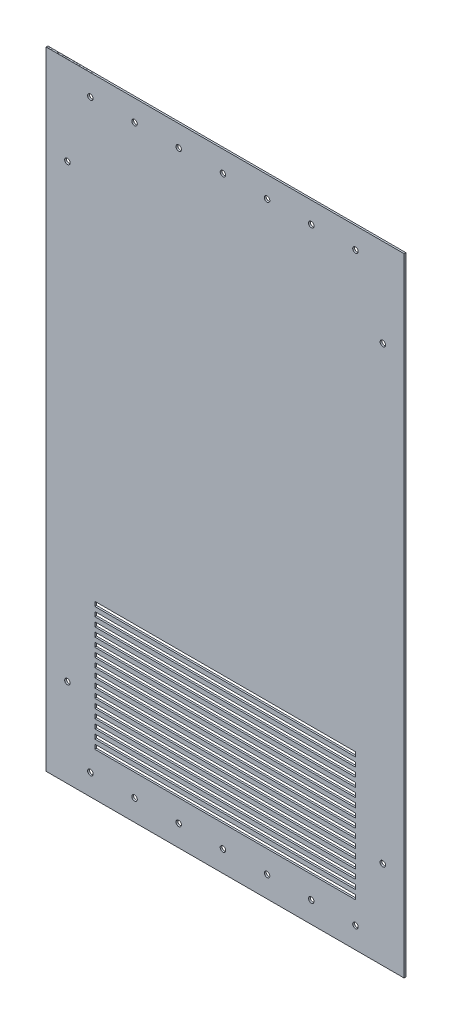
SolidWorks part; units mm, degrees
ref_plane "Front Plane" through (0, 0, 0) normal (0, 0, 1) x (1, 0, 0)
ref_plane "Top Plane" through (0, 0, 0) normal (0, 1, 0) x (1, 0, 0)
ref_plane "Right Plane" through (0, 0, 0) normal (1, 0, 0) x (0, 0, -1)
sketch "Sketch1" plane through (0, 0, 0) normal (0, 0, 1) x (1, 0, 0)
  line L0 (24, -100) -> (24, -571.3583) construction
  line L1 (0, 0) -> (405, 0)
  line L2 (0, 0) -> (0, -710)
  line L3 (0, -710) -> (405, -710)
  line L4 (405, 0) -> (405, -710)
  line L5 (24, -610) -> (381, -610) construction
  line L6 (381, -610) -> (381, -100) construction
  circle A0 centre (24, -100) radius 3.1
  circle A1 centre (381, -100) radius 3.1
  circle A2 centre (381, -610) radius 3.1
  circle A3 centre (24, -610) radius 3.1
  dimension "D8" = 6.2
  dimension "D1" = 405
  dimension "D2" = 710
  dimension "D3" = 24
  dimension "D4" = 100
  dimension "D5" = 24
  dimension "D6" = 100
  dimension "D7" = 100
extrude "Boss-Extrude1" add sketch "Sketch1" along normal blind 2
sketch "Sketch2" plane through (0, 0, 2) normal (0, 0, 1) x (1, 0, 0)
  line L0 (50, -24) -> (355, -24) construction
  line L1 (405, 0) -> (0, 0) construction
  line L2 (0, 0) -> (0, -710) construction
  line L3 (405, -710) -> (405, 0) construction
  line L4 (0, -355) -> (405, -355) construction
  line L5 (50, -686) -> (355, -686) construction
  circle A0 centre (50, -24) radius 3.1
  circle A1 centre (100, -24) radius 3.1
  circle A2 centre (150, -24) radius 3.1
  circle A3 centre (200, -24) radius 3.1
  circle A4 centre (250, -24) radius 3.1
  circle A5 centre (300, -24) radius 3.1
  circle A6 centre (350, -24) radius 3.1
  circle A7 centre (300, -686) radius 3.1
  circle A8 centre (250, -686) radius 3.1
  circle A9 centre (200, -686) radius 3.1
  circle A10 centre (150, -686) radius 3.1
  circle A11 centre (100, -686) radius 3.1
  circle A12 centre (50, -686) radius 3.1
  circle A13 centre (350, -686) radius 3.1
  dimension "D4" = 6.2
  dimension "D1" = 24
  dimension "D2" = 50
  dimension "D3" = 50
  dimension "D5" = 7
extrude "Cut-Extrude1" cut sketch "Sketch2" against normal through all
sketch "Sketch3" plane through (0, 0, 2) normal (0, 0, 1) x (1, 0, 0)
  line L0 (345.4109, -755.089) -> (399.6973, -755.089) construction
  line L1 (349.0904, -752.2312) -> (348.8156, -752.4415)
  line L2 (348.8156, -754.2364) -> (349.0904, -754.4446)
  line L3 (352.9045, -752.5313) -> (353.2186, -752.5313)
  line L4 (353.2186, -752.5313) -> (353.2186, -752.9758)
  line L5 (356.7186, -753.7035) -> (356.7186, -755.089)
  line L6 (356.7186, -755.089) -> (356.4045, -755.089)
  line L7 (356.4045, -755.089) -> (356.4045, -753.7021)
  line L8 (354.9686, -754.0941) -> (354.9686, -755.089)
  line L9 (354.9686, -755.089) -> (354.6545, -755.089)
  line L10 (354.6545, -755.089) -> (354.6545, -753.7884)
  line L11 (353.2186, -754.0127) -> (353.2186, -755.089)
  line L12 (353.2186, -755.089) -> (352.9045, -755.089)
  line L13 (352.9045, -755.089) -> (352.9045, -752.5313)
  line L14 (357.4366, -752.5313) -> (357.7507, -752.5313)
  line L15 (357.7507, -752.5313) -> (357.7507, -753.0045)
  line L16 (357.7507, -754.6255) -> (357.7507, -756.0313)
  line L17 (357.7507, -756.0313) -> (357.4366, -756.0313)
  line L18 (357.4366, -756.0313) -> (357.4366, -752.5313)
  line L19 (360.6673, -752.5313) -> (360.9814, -752.5313)
  line L20 (360.9814, -752.5313) -> (360.9814, -752.9078)
  line L21 (361.8789, -752.574) -> (361.7064, -752.8461)
  line L22 (360.9814, -754.2294) -> (360.9814, -755.089)
  line L23 (360.9814, -755.089) -> (360.6673, -755.089)
  line L24 (360.6673, -755.089) -> (360.6673, -752.5313)
  line L25 (364.2921, -754.2813) -> (364.5712, -754.4278)
  line L26 (364.7058, -753.8774) -> (362.4173, -753.8774)
  line L27 (362.4503, -753.5633) -> (364.3917, -753.5633)
  line L28 (366.5455, -752.8503) -> (366.3324, -753.0697)
  line L29 (365.1096, -754.7875) -> (365.3179, -754.5505)
  line L30 (368.4302, -752.8503) -> (368.217, -753.0697)
  line L31 (366.9943, -754.7875) -> (367.2025, -754.5505)
  line L32 (372.1994, -752.5313) -> (372.5135, -752.5313)
  line L33 (372.5135, -752.5313) -> (372.5135, -752.9078)
  line L34 (373.4109, -752.574) -> (373.2384, -752.8461)
  line L35 (372.5135, -754.2294) -> (372.5135, -755.089)
  line L36 (372.5135, -755.089) -> (372.1994, -755.089)
  line L37 (372.1994, -755.089) -> (372.1994, -752.5313)
  line L38 (376.2827, -752.8503) -> (376.0696, -753.0697)
  line L39 (374.8468, -754.7875) -> (375.0551, -754.5505)
  line L40 (376.9109, -752.5313) -> (377.225, -752.5313)
  line L41 (377.225, -752.5313) -> (377.225, -755.089)
  line L42 (377.225, -755.089) -> (376.9109, -755.089)
  line L43 (376.9109, -755.089) -> (376.9109, -752.5313)
  line L44 (380.5904, -751.4992) -> (380.5904, -755.089)
  line L45 (380.5904, -755.089) -> (380.2763, -755.089)
  line L46 (380.2763, -755.089) -> (380.2763, -754.6465)
  line L47 (380.2763, -753.0263) -> (380.2763, -751.4992)
  line L48 (380.2763, -751.4992) -> (380.5904, -751.4992)
  line L49 (383.4075, -754.2813) -> (383.6866, -754.4278)
  line L50 (383.8212, -753.8774) -> (381.5327, -753.8774)
  line L51 (381.5657, -753.5633) -> (383.5071, -753.5633)
  line L52 (388.3084, -753.0858) -> (388.0454, -753.2492)
  line L53 (388.0454, -754.371) -> (388.3084, -754.5435)
  line L54 (391.8532, -752.5313) -> (392.1933, -752.5313)
  line L55 (392.1933, -752.5313) -> (393.0423, -754.3934)
  line L56 (393.0423, -754.3934) -> (393.8914, -752.5313)
  line L57 (393.8914, -752.5313) -> (394.2314, -752.5313)
  line L58 (394.2314, -752.5313) -> (393.0648, -755.089)
  line L59 (393.0648, -755.089) -> (393.0199, -755.089)
  line L60 (393.0199, -755.089) -> (391.8532, -752.5313)
  line L61 (396.8691, -754.2813) -> (397.1481, -754.4278)
  line L62 (397.2827, -753.8774) -> (394.9943, -753.8774)
  line L63 (395.0272, -753.5633) -> (396.9686, -753.5633)
  line L64 (397.8212, -752.5313) -> (398.1353, -752.5313)
  line L65 (398.1353, -752.5313) -> (398.1353, -752.9078)
  line L66 (399.0327, -752.574) -> (398.8602, -752.8461)
  line L67 (398.1353, -754.2294) -> (398.1353, -755.089)
  line L68 (398.1353, -755.089) -> (397.8212, -755.089)
  line L69 (397.8212, -755.089) -> (397.8212, -752.5313)
  spline S0 degree 3 poles (348.8156, -752.4415) (348.7773, -752.3945) (348.7167, -752.3273) (348.629, -752.2455) (348.5611, -752.1882) (348.4894, -752.1368) (348.4155, -752.0886) (348.3383, -752.0453) (348.2316, -751.9928) (348.0919, -751.9381) (347.8544, -751.8758) (347.6689, -751.8576) (347.5437, -751.8582) knots 0 0 0 0 0.125475 0.187121 0.248294 0.309295 0.36985 0.430973 0.492456 0.616148 0.740844 1 1 1 1
  spline S1 degree 3 poles (347.5437, -751.8582) (347.4739, -751.8573) (347.3699, -751.8648) (347.2334, -751.8849) (347.1337, -751.907) (347.0362, -751.935) (346.9401, -751.9684) (346.8469, -752.0098) (346.7552, -752.0555) (346.6675, -752.1071) (346.5844, -752.1634) (346.5064, -752.2238) (346.4333, -752.2885) (346.3651, -752.3571) (346.3023, -752.4305) (346.2452, -752.5083) (346.1924, -752.5896) (346.1452, -752.6742) (346.1057, -752.7622) (346.0707, -752.8524) (346.043, -752.9455) (346.0211, -753.041) (346.0006, -753.1732) (345.9934, -753.2742) (345.9943, -753.3425) knots 0 0 0 0 0.087502 0.130463 0.172752 0.215403 0.25765 0.300153 0.343121 0.385925 0.427686 0.468818 0.509492 0.549883 0.58998 0.630405 0.670869 0.711384 0.751627 0.791776 0.832459 0.873319 0.914543 1 1 1 1
  spline S2 degree 3 poles (345.9943, -753.3425) (345.9938, -753.4441) (346.0079, -753.5941) (346.0536, -753.787) (346.1038, -753.9224) (346.1657, -754.0523) (346.2439, -754.1746) (346.3345, -754.291) (346.4388, -754.3988) (346.5532, -754.4974) (346.676, -754.5841) (346.8068, -754.6564) (346.9441, -754.7166) (347.0892, -754.7628) (347.2958, -754.8072) (347.4565, -754.8206) (347.5655, -754.8197) knots 0 0 0 0 0.12629 0.186726 0.246146 0.305576 0.365429 0.426326 0.48884 0.551725 0.613919 0.675484 0.737334 0.800229 0.864502 1 1 1 1
  spline S3 degree 3 poles (347.5655, -754.8197) (347.6856, -754.8198) (347.8641, -754.8028) (348.092, -754.7408) (348.2534, -754.677) (348.4067, -754.5939) (348.6042, -754.4576) (348.7349, -754.3292) (348.8156, -754.2364) knots 0 0 0 0 0.252949 0.374755 0.49594 0.617181 0.740909 1 1 1 1
  spline S4 degree 3 poles (349.0904, -754.4446) (349.0471, -754.5022) (348.9783, -754.5848) (348.8774, -754.6859) (348.7978, -754.756) (348.7147, -754.8222) (348.6266, -754.8825) (348.5347, -754.9378) (348.4394, -754.9884) (348.3406, -755.0333) (348.2386, -755.0718) (348.1338, -755.1049) (348.0261, -755.1321) (347.9154, -755.1534) (347.7626, -755.1727) (347.646, -755.1793) (347.5676, -755.1787) knots 0 0 0 0 0.123053 0.183475 0.243727 0.304279 0.364863 0.425946 0.487391 0.54922 0.611144 0.673529 0.736961 0.800785 0.866013 1 1 1 1
  spline S5 degree 3 poles (347.5676, -755.1787) (347.4931, -755.1796) (347.383, -755.1737) (347.2386, -755.1581) (347.1348, -755.1408) (347.0337, -755.1205) (346.9361, -755.0932) (346.8412, -755.0627) (346.7492, -755.0268) (346.6602, -754.9863) (346.5743, -754.9405) (346.4917, -754.8898) (346.4115, -754.8353) (346.3349, -754.7753) (346.236, -754.6887) (346.167, -754.6173) (346.124, -754.5666) knots 0 0 0 0 0.13775 0.203917 0.26878 0.332414 0.394754 0.45618 0.516996 0.577396 0.637198 0.696999 0.756756 0.816554 0.876948 1 1 1 1
  spline S6 degree 3 poles (346.124, -754.5666) (346.0514, -754.4819) (345.954, -754.3461) (345.8508, -754.1497) (345.7884, -753.9964) (345.7397, -753.8363) (345.6937, -753.6109) (345.6798, -753.4365) (345.6802, -753.3186) knots 0 0 0 0 0.247156 0.36878 0.490734 0.613614 0.738958 1 1 1 1
  spline S7 degree 3 poles (345.6802, -753.3186) (345.6801, -753.1948) (345.6958, -753.0113) (345.7526, -752.7759) (345.812, -752.6097) (345.8873, -752.4505) (345.9803, -752.2997) (346.09, -752.1562) (346.2154, -752.0222) (346.353, -751.8996) (346.5003, -751.7918) (346.6571, -751.7021) (346.8216, -751.6271) (346.9951, -751.5695) (347.2417, -751.5146) (347.4336, -751.4995) (347.5634, -751.4992) knots 0 0 0 0 0.127014 0.187955 0.248014 0.307748 0.368235 0.42947 0.492743 0.556258 0.618217 0.679655 0.741246 0.803415 0.866815 1 1 1 1
  spline S8 degree 3 poles (347.5634, -751.4992) (347.6429, -751.4991) (347.7611, -751.5045) (347.9156, -751.5255) (348.0272, -751.5466) (348.1363, -751.5728) (348.2421, -751.6069) (348.3452, -751.646) (348.445, -751.6909) (348.5409, -751.7414) (348.6329, -751.7968) (348.7204, -751.8571) (348.8039, -751.9218) (348.882, -751.9922) (348.9822, -752.0913) (349.0482, -752.1745) (349.0904, -752.2312) knots 0 0 0 0 0.135683 0.201215 0.265682 0.329267 0.392395 0.45507 0.517127 0.57879 0.63974 0.700192 0.759806 0.819628 0.879355 1 1 1 1
  spline S9 degree 3 poles (350.954, -752.4864) (351.0481, -752.4854) (351.1873, -752.499) (351.3654, -752.5436) (351.4912, -752.5888) (351.6096, -752.6496) (351.762, -752.7471) (351.8636, -752.8398) (351.9257, -752.9078) knots 0 0 0 0 0.258332 0.382134 0.503804 0.624693 0.746871 1 1 1 1
  spline S10 degree 3 poles (351.9257, -752.9078) (351.9828, -752.9701) (352.0592, -753.07) (352.1414, -753.2144) (352.1905, -753.3266) (352.2292, -753.443) (352.2663, -753.6059) (352.2758, -753.7322) (352.2763, -753.8171) knots 0 0 0 0 0.253834 0.376506 0.498534 0.621368 0.744565 1 1 1 1
  spline S11 degree 3 poles (352.2763, -753.8171) (352.2768, -753.9027) (352.2651, -754.0298) (352.2265, -754.1942) (352.1857, -754.3121) (352.1333, -754.4259) (352.0694, -754.5353) (351.9936, -754.6405) (351.9076, -754.7405) (351.8125, -754.8327) (351.7094, -754.913) (351.6002, -754.9818) (351.4836, -755.0373) (351.3605, -755.0809) (351.1845, -755.1228) (351.0469, -755.1335) (350.954, -755.1338) knots 0 0 0 0 0.123337 0.183265 0.243172 0.302898 0.363774 0.425605 0.489659 0.553785 0.616222 0.677854 0.739517 0.802097 0.865866 1 1 1 1
  spline S12 degree 3 poles (350.954, -755.1338) (350.8606, -755.1334) (350.7226, -755.1229) (350.546, -755.0809) (350.4228, -755.0371) (350.3057, -754.9818) (350.1959, -754.9132) (350.0927, -754.8326) (349.9976, -754.7405) (349.9116, -754.6405) (349.8357, -754.5353) (349.7719, -754.4259) (349.7195, -754.3121) (349.6787, -754.1942) (349.6401, -754.0298) (349.6284, -753.9027) (349.6289, -753.8171) knots 0 0 0 0 0.134635 0.198324 0.260825 0.322714 0.384555 0.446913 0.510958 0.574931 0.636685 0.697483 0.757134 0.816966 0.876818 1 1 1 1
  spline S13 degree 3 poles (349.6289, -753.8171) (349.6294, -753.7324) (349.6389, -753.6064) (349.6759, -753.4439) (349.7146, -753.328) (349.7642, -753.2162) (349.8453, -753.0715) (349.923, -752.9724) (349.9794, -752.9099) knots 0 0 0 0 0.255238 0.378679 0.501088 0.622714 0.746241 1 1 1 1
  spline S14 degree 3 poles (349.9794, -752.9099) (350.041, -752.841) (350.1436, -752.7492) (350.2956, -752.6497) (350.4153, -752.5901) (350.5409, -752.5434) (350.7198, -752.499) (350.8594, -752.4855) (350.954, -752.4864) knots 0 0 0 0 0.252713 0.374819 0.496436 0.617911 0.741288 1 1 1 1
  spline S15 degree 3 poles (350.9526, -752.8005) (350.8856, -752.8007) (350.7861, -752.8097) (350.6581, -752.8408) (350.5667, -752.8734) (350.479, -752.9155) (350.3951, -752.9672) (350.3147, -753.0278) (350.2393, -753.0973) (350.1701, -753.1732) (350.1096, -753.254) (350.0582, -753.3385) (350.0154, -753.4268) (349.9835, -753.5197) (349.952, -753.6499) (349.9432, -753.7511) (349.943, -753.8192) knots 0 0 0 0 0.126044 0.187165 0.247399 0.30838 0.36978 0.432584 0.497641 0.562401 0.625557 0.687332 0.748313 0.809791 0.871768 1 1 1 1
  spline S16 degree 3 poles (349.943, -753.8192) (349.9432, -753.9079) (349.9588, -754.0412) (350.0171, -754.2092) (350.0757, -754.3288) (350.1491, -754.4395) (350.2356, -754.5382) (350.3342, -754.6233) (350.4438, -754.694) (350.5622, -754.7501) (350.7306, -754.804) (350.8633, -754.8207) (350.9526, -754.8197) knots 0 0 0 0 0.168179 0.251488 0.335841 0.419834 0.502345 0.583649 0.665931 0.748717 0.831047 1 1 1 1
  spline S17 degree 3 poles (350.9526, -754.8197) (351.0419, -754.8206) (351.1744, -754.8042) (351.3425, -754.7499) (351.4607, -754.6941) (351.5703, -754.6231) (351.6696, -754.5386) (351.7554, -754.4392) (351.8287, -754.3287) (351.8882, -754.2094) (351.9462, -754.0412) (351.962, -753.9079) (351.9622, -753.8192) knots 0 0 0 0 0.168983 0.250908 0.333708 0.416005 0.49766 0.579893 0.663902 0.748466 0.831791 1 1 1 1
  spline S18 degree 3 poles (351.9622, -753.8192) (351.962, -753.7511) (351.9531, -753.6499) (351.9217, -753.5197) (351.8898, -753.4268) (351.8471, -753.3383) (351.7947, -753.2543) (351.7345, -753.1729) (351.6644, -753.0975) (351.5891, -753.0278) (351.5087, -752.9672) (351.4249, -752.9157) (351.3375, -752.873) (351.2461, -752.8411) (351.1185, -752.8095) (351.0193, -752.8008) (350.9526, -752.8005) knots 0 0 0 0 0.128274 0.19027 0.251768 0.312769 0.374793 0.43797 0.503047 0.568125 0.63095 0.692369 0.752973 0.813641 0.874355 1 1 1 1
  spline S19 degree 3 poles (353.2186, -752.9758) (353.2713, -752.9003) (353.3777, -752.7674) (353.5077, -752.6573) (353.5734, -752.6161) knots 0 0 0 0 0.543395 1 1 1 1
  spline S20 degree 3 poles (353.5734, -752.6161) (353.655, -752.574) (353.8268, -752.5073) (354.0099, -752.4871) (354.1006, -752.4864) knots 0 0 0 0 0.503035 1 1 1 1
  spline S21 degree 3 poles (354.1006, -752.4864) (354.1617, -752.4872) (354.2533, -752.4949) (354.3711, -752.5263) (354.4557, -752.5586) (354.5354, -752.5979) (354.6085, -752.6439) (354.6741, -752.6956) (354.7323, -752.7553) (354.7845, -752.8246) (354.8523, -752.9384) (354.8911, -753.0355) (354.9146, -753.1041) knots 0 0 0 0 0.166532 0.248836 0.331246 0.412957 0.490494 0.566156 0.639987 0.716765 0.802144 1 1 1 1
  spline S22 degree 3 poles (354.9146, -753.1041) (354.9407, -753.055) (354.9838, -752.9846) (355.0481, -752.8974) (355.0981, -752.8374) (355.1506, -752.7821) (355.2056, -752.7313) (355.263, -752.6848) (355.3428, -752.6305) (355.4466, -752.5729) (355.6212, -752.5057) (355.7604, -752.4862) (355.8527, -752.4864) knots 0 0 0 0 0.141226 0.209116 0.27484 0.339483 0.402476 0.464942 0.526833 0.647415 0.765562 1 1 1 1
  spline S23 degree 3 poles (355.8527, -752.4864) (355.9364, -752.487) (356.0614, -752.5007) (356.2157, -752.5587) (356.3211, -752.6169) (356.4163, -752.6901) (356.499, -752.7772) (356.5688, -752.8775) (356.6144, -752.9719) (356.6453, -753.0553) (356.6643, -753.1263) (356.6812, -753.2044) (356.6952, -753.2898) (356.7054, -753.3827) (356.7159, -753.5213) (356.719, -753.6292) (356.7186, -753.7035) knots 0 0 0 0 0.147965 0.218797 0.28947 0.359724 0.429708 0.500497 0.574429 0.613947 0.657155 0.703973 0.754939 0.809707 0.868833 1 1 1 1
  spline S24 degree 3 poles (356.4045, -753.7021) (356.4046, -753.6393) (356.4036, -753.5489) (356.3965, -753.434) (356.3906, -753.3598) (356.3823, -753.2936) (356.3717, -753.2354) (356.3604, -753.1848) (356.3417, -753.1287) (356.3117, -753.0668) (356.2661, -753.0001) (356.2086, -752.942) (356.1423, -752.8916) (356.0667, -752.8507) (355.9529, -752.8104) (355.8605, -752.8001) (355.798, -752.8005) knots 0 0 0 0 0.150563 0.216151 0.27568 0.328707 0.375904 0.417302 0.452693 0.517265 0.581217 0.645322 0.712024 0.78013 0.850218 1 1 1 1
  spline S25 degree 3 poles (355.798, -752.8005) (355.7195, -752.7991) (355.6025, -752.8184) (355.4556, -752.8764) (355.3533, -752.9388) (355.2593, -753.0136) (355.1784, -753.1026) (355.1116, -753.2032) (355.0663, -753.2963) (355.0377, -753.38) (355.0189, -753.4531) (355.0042, -753.5362) (354.9904, -753.6287) (354.9814, -753.7313) (354.9701, -753.8872) (354.9691, -754.0095) (354.9686, -754.0941) knots 0 0 0 0 0.134707 0.201865 0.270788 0.340024 0.408083 0.476813 0.547346 0.58564 0.628865 0.677153 0.730803 0.789807 0.854325 1 1 1 1
  spline S26 degree 3 poles (354.6545, -753.7884) (354.6546, -753.7178) (354.6536, -753.6165) (354.6465, -753.4878) (354.6406, -753.405) (354.6322, -753.3315) (354.6226, -753.2671) (354.6112, -753.2119) (354.5924, -753.1514) (354.5637, -753.0846) (354.5175, -753.0135) (354.4599, -752.9512) (354.3923, -752.8981) (354.3163, -752.8542) (354.202, -752.8109) (354.1086, -752.801) (354.0459, -752.8005) knots 0 0 0 0 0.158779 0.227738 0.289946 0.345499 0.393896 0.436374 0.472122 0.536384 0.599078 0.661948 0.726311 0.791771 0.858647 1 1 1 1
  spline S27 degree 3 poles (354.0459, -752.8005) (353.9701, -752.7999) (353.8562, -752.8181) (353.7134, -752.8756) (353.6114, -752.9352) (353.5177, -753.0091) (353.4357, -753.096) (353.3668, -753.1949) (353.3211, -753.287) (353.2916, -753.3686) (353.272, -753.4379) (353.2551, -753.5149) (353.2426, -753.5998) (353.2305, -753.6921) (353.2224, -753.8306) (353.2176, -753.9383) (353.2186, -754.0127) knots 0 0 0 0 0.136871 0.206114 0.277538 0.349772 0.421251 0.492911 0.567027 0.606614 0.649704 0.697303 0.749086 0.804881 0.865485 1 1 1 1
  spline S28 degree 3 poles (357.7507, -753.0045) (357.8128, -752.9192) (357.9173, -752.8033) (358.0785, -752.6791) (358.2057, -752.6077) (358.3401, -752.5539) (358.5313, -752.4998) (358.6824, -752.4867) (358.7841, -752.4864) knots 0 0 0 0 0.263045 0.386061 0.505771 0.625178 0.746148 1 1 1 1
  spline S29 degree 3 poles (358.7841, -752.4864) (358.8738, -752.4873) (359.007, -752.4972) (359.1785, -752.538) (359.3, -752.5814) (359.4173, -752.635) (359.5285, -752.7028) (359.6354, -752.7812) (359.7354, -752.8714) (359.8277, -752.969) (359.9075, -753.0741) (359.9764, -753.183) (360.0321, -753.2976) (360.0756, -753.4169) (360.1176, -753.5847) (360.1284, -753.7153) (360.1289, -753.8031) knots 0 0 0 0 0.128636 0.190653 0.252125 0.313446 0.375227 0.438498 0.503285 0.56801 0.630879 0.692154 0.752552 0.813191 0.873985 1 1 1 1
  spline S30 degree 3 poles (360.1289, -753.8031) (360.1287, -753.8926) (360.1171, -754.0253) (360.0765, -754.196) (360.0335, -754.3173) (359.9778, -754.4333) (359.9101, -754.5439) (359.8302, -754.6491) (359.7389, -754.7474) (359.6399, -754.838) (359.534, -754.9173) (359.4229, -754.9838) (359.3073, -755.0394) (359.186, -755.0812) (359.0157, -755.1222) (358.8832, -755.1335) (358.7939, -755.1338) knots 0 0 0 0 0.128034 0.189574 0.25058 0.311733 0.37325 0.435763 0.500346 0.564949 0.627528 0.689157 0.749865 0.81076 0.8723 1 1 1 1
  spline S31 degree 3 poles (358.7939, -755.1338) (358.6935, -755.135) (358.545, -755.1178) (358.3546, -755.0653) (358.2204, -755.0086) (358.0923, -754.9363) (357.9272, -754.8168) (357.8182, -754.7057) (357.7507, -754.6255) knots 0 0 0 0 0.250548 0.37123 0.492116 0.613401 0.737997 1 1 1 1
  spline S32 degree 3 poles (358.7813, -752.8005) (358.7112, -752.7995) (358.6078, -752.8095) (358.4741, -752.8391) (358.38, -752.872) (358.2897, -752.9124) (358.2041, -752.9629) (358.123, -753.0226) (358.0468, -753.0902) (357.9779, -753.1648) (357.917, -753.2444) (357.8657, -753.3289) (357.8232, -753.4175) (357.7909, -753.511) (357.7597, -753.6431) (357.7509, -753.7462) (357.7507, -753.8157) knots 0 0 0 0 0.130024 0.192374 0.253884 0.314896 0.375806 0.438242 0.501591 0.564881 0.626533 0.687516 0.748106 0.808796 0.870822 1 1 1 1
  spline S33 degree 3 poles (357.7507, -753.8157) (357.7508, -753.9065) (357.766, -754.0416) (357.822, -754.2114) (357.8805, -754.3289) (357.9544, -754.4369) (358.0435, -754.5336) (358.147, -754.6183) (358.263, -754.6898) (358.3875, -754.7477) (358.5606, -754.8034) (358.6961, -754.8196) (358.7862, -754.8197) knots 0 0 0 0 0.169344 0.251061 0.332326 0.413189 0.494299 0.576654 0.661785 0.747765 0.831967 1 1 1 1
  spline S34 degree 3 poles (358.7862, -754.8197) (358.8747, -754.8203) (359.0069, -754.8024) (359.1758, -754.7474) (359.296, -754.688) (359.4088, -754.6149) (359.5107, -754.5274) (359.5997, -754.4259) (359.6756, -754.3129) (359.7366, -754.1917) (359.7979, -754.0253) (359.8138, -753.8934) (359.8148, -753.8066) knots 0 0 0 0 0.165574 0.248159 0.332033 0.416257 0.499525 0.583039 0.668596 0.754035 0.83692 1 1 1 1
  spline S35 degree 3 poles (359.8148, -753.8066) (359.816, -753.7191) (359.7964, -753.5882) (359.7389, -753.4207) (359.6764, -753.3012) (359.6022, -753.1884) (359.5125, -753.0889) (359.4118, -753.0017) (359.2992, -752.9297) (359.1782, -752.8725) (359.0072, -752.8159) (358.8718, -752.8009) (358.7813, -752.8005) knots 0 0 0 0 0.163349 0.245826 0.330367 0.415198 0.497941 0.580476 0.66374 0.747513 0.830399 1 1 1 1
  spline S36 degree 3 poles (360.9814, -752.9078) (361.0245, -752.8401) (361.0924, -752.7463) (361.1982, -752.6436) (361.2758, -752.5851) (361.3562, -752.5413) (361.4638, -752.4986) (361.5494, -752.4868) (361.6054, -752.4864) knots 0 0 0 0 0.306112 0.438367 0.560541 0.675317 0.786114 1 1 1 1
  spline S37 degree 3 poles (361.6054, -752.4864) (361.6504, -752.4867) (361.7469, -752.5036) (361.8345, -752.5472) (361.8789, -752.574) knots 0 0 0 0 0.463523 1 1 1 1
  spline S38 degree 3 poles (361.7064, -752.8461) (361.6778, -752.8334) (361.6263, -752.8101) (361.5705, -752.8008) (361.5458, -752.8005) knots 0 0 0 0 0.56023 1 1 1 1
  spline S39 degree 3 poles (361.5458, -752.8005) (361.4943, -752.8004) (361.4154, -752.8193) (361.3205, -752.8761) (361.2623, -752.9243) (361.2173, -752.9709) (361.1851, -753.0115) (361.1557, -753.0571) (361.1275, -753.1068) (361.1018, -753.1616) (361.069, -753.2426) (361.0494, -753.3071) (361.0375, -753.3516) knots 0 0 0 0 0.191338 0.295191 0.410312 0.47193 0.536425 0.603119 0.674118 0.749332 0.828283 1 1 1 1
  spline S40 degree 3 poles (361.0375, -753.3516) (361.0258, -753.3962) (361.0143, -753.4714) (361.0021, -753.5811) (360.9949, -753.6841) (360.9884, -753.8007) (360.9831, -753.984) (360.9809, -754.1284) (360.9814, -754.2294) knots 0 0 0 0 0.156938 0.2586 0.375891 0.508166 0.656238 1 1 1 1
  spline S41 degree 3 poles (364.5712, -754.4278) (364.5297, -754.5055) (364.4602, -754.6145) (364.3533, -754.7442) (364.2682, -754.826) (364.1785, -754.8972) (364.0838, -754.9596) (363.9835, -755.0127) (363.8776, -755.0575) (363.7653, -755.0918) (363.603, -755.1252) (363.4761, -755.1338) (363.3898, -755.1338) knots 0 0 0 0 0.181661 0.265874 0.346355 0.4246 0.501903 0.579992 0.658443 0.738672 0.821894 1 1 1 1
  spline S42 degree 3 poles (363.3898, -755.1338) (363.294, -755.1338) (363.1531, -755.1228) (362.9739, -755.0796) (362.8507, -755.0357) (362.7359, -754.9783) (362.6294, -754.9083) (362.5306, -754.8262) (362.4426, -754.7312) (362.3633, -754.6295) (362.2934, -754.5235) (362.2349, -754.4136) (362.1874, -754.3003) (362.149, -754.1844) (362.1129, -754.024) (362.1041, -753.9001) (362.1032, -753.8171) knots 0 0 0 0 0.139629 0.204797 0.268135 0.329814 0.391301 0.453434 0.516552 0.579631 0.641119 0.701294 0.76081 0.819932 0.87892 1 1 1 1
  spline S43 degree 3 poles (362.1032, -753.8171) (362.1042, -753.7393) (362.1115, -753.6232) (362.1431, -753.4727) (362.1752, -753.3638) (362.2168, -753.2582) (362.285, -753.1207) (362.3501, -753.0246) (362.3977, -752.9632) knots 0 0 0 0 0.253768 0.377428 0.500551 0.623296 0.746578 1 1 1 1
  spline S44 degree 3 poles (362.3977, -752.9632) (362.4583, -752.8874) (362.557, -752.7815) (362.7117, -752.6708) (362.8333, -752.6027) (362.9636, -752.5511) (363.1502, -752.4986) (363.298, -752.4876) (363.3975, -752.4864) knots 0 0 0 0 0.253589 0.374643 0.49534 0.616325 0.739759 1 1 1 1
  spline S45 degree 3 poles (363.3975, -752.4864) (363.5003, -752.486) (363.6522, -752.5008) (363.8448, -752.5541) (363.9787, -752.6092) (364.1043, -752.6804) (364.2626, -752.7995) (364.3661, -752.9091) (364.4274, -752.9898) knots 0 0 0 0 0.259033 0.38188 0.502258 0.622752 0.744743 1 1 1 1
  spline S46 degree 3 poles (364.4274, -752.9898) (364.4733, -753.0487) (364.5332, -753.1443) (364.5969, -753.2811) (364.6352, -753.39) (364.6662, -753.5038) (364.6968, -753.6662) (364.7042, -753.7922) (364.7058, -753.8774) knots 0 0 0 0 0.236255 0.356174 0.47725 0.60154 0.729618 1 1 1 1
  spline S47 degree 3 poles (362.4173, -753.8774) (362.4191, -753.9437) (362.428, -754.0415) (362.4583, -754.1667) (362.4895, -754.2538) (362.5274, -754.3367) (362.5738, -754.4149) (362.6291, -754.4879) (362.6908, -754.5565) (362.7596, -754.6176) (362.8318, -754.6722) (362.9087, -754.718) (362.9896, -754.7552) (363.0744, -754.7843) (363.1944, -754.8114) (363.2875, -754.8201) (363.3505, -754.8197) knots 0 0 0 0 0.134476 0.198391 0.260753 0.321829 0.383037 0.444653 0.507398 0.569825 0.630778 0.690929 0.750945 0.811049 0.872331 1 1 1 1
  spline S48 degree 3 poles (363.3505, -754.8197) (363.4127, -754.82) (363.506, -754.8127) (363.6279, -754.7872) (363.7171, -754.7613) (363.8027, -754.7297) (363.8819, -754.6916) (363.9548, -754.6495) (364.0229, -754.6013) (364.089, -754.5423) (364.1825, -754.4374) (364.2496, -754.3478) (364.2921, -754.2813) knots 0 0 0 0 0.163879 0.245659 0.327726 0.40861 0.485749 0.559169 0.630268 0.705306 0.792065 1 1 1 1
  spline S49 degree 3 poles (364.3917, -753.5633) (364.3718, -753.4826) (364.3322, -753.3687) (364.2597, -753.2317) (364.1981, -753.1462) (364.1283, -753.0702) (364.0477, -753.0037) (363.9572, -752.9443) (363.8575, -752.8941) (363.7518, -752.8515) (363.604, -752.813) (363.4901, -752.7994) (363.4136, -752.8005) knots 0 0 0 0 0.185231 0.267501 0.3444 0.419595 0.496891 0.576638 0.660268 0.745387 0.83004 1 1 1 1
  spline S50 degree 3 poles (363.4136, -752.8005) (363.3517, -752.8003) (363.2597, -752.807) (363.1413, -752.8328) (363.0566, -752.8587) (362.976, -752.8933) (362.871, -752.9477) (362.8001, -753.002) (362.7546, -753.0403) knots 0 0 0 0 0.259141 0.384162 0.505992 0.629098 0.750669 1 1 1 1
  spline S51 degree 3 poles (362.7546, -753.0403) (362.7197, -753.0697) (362.6725, -753.1205) (362.6158, -753.1953) (362.5764, -753.2583) (362.5403, -753.327) (362.4941, -753.4276) (362.4667, -753.508) (362.4503, -753.5633) knots 0 0 0 0 0.22258 0.3385 0.458709 0.585535 0.717518 1 1 1 1
  spline S52 degree 3 poles (366.3324, -753.0697) (366.2976, -753.0282) (366.2441, -752.9703) (366.1663, -752.9063) (366.1112, -752.8673) (366.0558, -752.8379) (365.9837, -752.8096) (365.9275, -752.8005) (365.8907, -752.8005) knots 0 0 0 0 0.305036 0.441309 0.565963 0.683525 0.793334 1 1 1 1
  spline S53 degree 3 poles (365.8907, -752.8005) (365.847, -752.7996) (365.7819, -752.8137) (365.7046, -752.8573) (365.6544, -752.9032) (365.612, -752.9559) (365.5703, -753.0348) (365.5585, -753.1008) (365.5584, -753.1447) knots 0 0 0 0 0.245901 0.369166 0.498511 0.628504 0.751028 1 1 1 1
  spline S54 degree 3 poles (365.5584, -753.1447) (365.5584, -753.1851) (365.5741, -753.2693) (365.6186, -753.3423) (365.6453, -753.3768) knots 0 0 0 0 0.479403 1 1 1 1
  spline S55 degree 3 poles (365.6453, -753.3768) (365.6613, -753.3985) (365.6925, -753.4281) (365.7381, -753.4682) (365.7814, -753.5002) (365.8301, -753.5338) (365.907, -753.5812) (365.9672, -753.6178) (366.0106, -753.6404) knots 0 0 0 0 0.17756 0.283982 0.402217 0.533568 0.676121 1 1 1 1
  spline S56 degree 3 poles (366.0106, -753.6404) (366.0633, -753.6696) (366.1392, -753.7134) (366.2328, -753.7763) (366.2943, -753.8209) (366.3482, -753.8661) (366.4099, -753.9223) (366.4491, -753.9681) (366.4712, -753.9994) knots 0 0 0 0 0.307115 0.446213 0.574876 0.694152 0.804581 1 1 1 1
  spline S57 degree 3 poles (366.4712, -753.9994) (366.5093, -754.0569) (366.5733, -754.1836) (366.5894, -754.3246) (366.5904, -754.3948) knots 0 0 0 0 0.495235 1 1 1 1
  spline S58 degree 3 poles (366.5904, -754.3948) (366.5899, -754.4446) (366.5844, -754.5186) (366.5614, -754.6134) (366.5384, -754.6811) (366.5072, -754.745) (366.4706, -754.8069) (366.4268, -754.8652) (366.3767, -754.9201) (366.3218, -754.9702) (366.2633, -755.0142) (366.2011, -755.0508) (366.1355, -755.081) (366.0666, -755.1051) (365.9686, -755.1277) (365.8923, -755.1335) (365.8409, -755.1338) knots 0 0 0 0 0.127199 0.188597 0.24864 0.309525 0.370037 0.431889 0.495704 0.559519 0.621372 0.682397 0.743568 0.805498 0.86864 1 1 1 1
  spline S59 degree 3 poles (365.8409, -755.1338) (365.7706, -755.1344) (365.6655, -755.1222) (365.5299, -755.0835) (365.4315, -755.0439) (365.3385, -754.9937) (365.2253, -754.9141) (365.1519, -754.8411) (365.1096, -754.7875) knots 0 0 0 0 0.251724 0.377219 0.504694 0.631458 0.755401 1 1 1 1
  spline S60 degree 3 poles (365.3179, -754.5505) (365.3555, -754.5924) (365.4138, -754.6511) (365.4997, -754.7146) (365.5625, -754.7532) (365.6267, -754.783) (365.7132, -754.8109) (365.7803, -754.8199) (365.8248, -754.8197) knots 0 0 0 0 0.285904 0.417172 0.540501 0.659238 0.775006 1 1 1 1
  spline S61 degree 3 poles (365.8248, -754.8197) (365.884, -754.8202) (365.9718, -754.8049) (366.0775, -754.7532) (366.1456, -754.6992) (366.2034, -754.6362) (366.2595, -754.5419) (366.2766, -754.4614) (366.2763, -754.4082) knots 0 0 0 0 0.261896 0.387836 0.517686 0.644509 0.764718 1 1 1 1
  spline S62 degree 3 poles (366.2763, -754.4082) (366.2761, -754.3642) (366.2621, -754.2759) (366.218, -754.1981) (366.1901, -754.1642) knots 0 0 0 0 0.500453 1 1 1 1
  spline S63 degree 3 poles (366.1901, -754.1642) (366.1732, -754.1439) (366.142, -754.1145) (366.0941, -754.0764) (366.049, -754.0441) (365.997, -754.0105) (365.9143, -753.9619) (365.8487, -753.925) (365.8023, -753.9006) knots 0 0 0 0 0.167462 0.27227 0.389551 0.520801 0.666263 1 1 1 1
  spline S64 degree 3 poles (365.8023, -753.9006) (365.7518, -753.8726) (365.6788, -753.8309) (365.5897, -753.7692) (365.5306, -753.7263) (365.4785, -753.6829) (365.4205, -753.6265) (365.3823, -753.5825) (365.3613, -753.5514) knots 0 0 0 0 0.30595 0.443775 0.572824 0.692154 0.802296 1 1 1 1
  spline S65 degree 3 poles (365.3613, -753.5514) (365.3221, -753.495) (365.2637, -753.3671) (365.243, -753.2281) (365.2443, -753.1574) knots 0 0 0 0 0.492591 1 1 1 1
  spline S66 degree 3 poles (365.2443, -753.1574) (365.2446, -753.1112) (365.2487, -753.0426) (365.2694, -752.955) (365.2884, -752.8929) (365.3149, -752.8344) (365.3466, -752.7787) (365.3837, -752.726) (365.4266, -752.677) (365.4737, -752.6325) (365.5246, -752.5937) (365.5781, -752.5606) (365.6345, -752.5328) (365.6944, -752.5118) (365.7795, -752.4921) (365.8458, -752.4859) (365.8907, -752.4864) knots 0 0 0 0 0.133044 0.196507 0.258613 0.319728 0.380873 0.442636 0.505079 0.567881 0.628814 0.68891 0.748765 0.809386 0.870884 1 1 1 1
  spline S67 degree 3 poles (365.8907, -752.4864) (365.9456, -752.4864) (366.0295, -752.4981) (366.1374, -752.5366) (366.2197, -752.5768) (366.3015, -752.6289) (366.415, -752.7158) (366.4949, -752.793) (366.5455, -752.8503) knots 0 0 0 0 0.213412 0.326127 0.444452 0.569061 0.702712 1 1 1 1
  spline S68 degree 3 poles (368.217, -753.0697) (368.1822, -753.0282) (368.1287, -752.9703) (368.0509, -752.9063) (367.9959, -752.8673) (367.9404, -752.8379) (367.8683, -752.8096) (367.8121, -752.8005) (367.7753, -752.8005) knots 0 0 0 0 0.305036 0.441309 0.565963 0.683525 0.793334 1 1 1 1
  spline S69 degree 3 poles (367.7753, -752.8005) (367.7317, -752.7996) (367.6665, -752.8137) (367.5892, -752.8573) (367.5391, -752.9032) (367.4966, -752.9559) (367.4549, -753.0348) (367.4431, -753.1008) (367.443, -753.1447) knots 0 0 0 0 0.245901 0.369166 0.498511 0.628504 0.751028 1 1 1 1
  spline S70 degree 3 poles (367.443, -753.1447) (367.443, -753.1851) (367.4587, -753.2693) (367.5032, -753.3423) (367.5299, -753.3768) knots 0 0 0 0 0.479403 1 1 1 1
  spline S71 degree 3 poles (367.5299, -753.3768) (367.5459, -753.3985) (367.5771, -753.4281) (367.6227, -753.4682) (367.666, -753.5002) (367.7147, -753.5338) (367.7916, -753.5812) (367.8518, -753.6178) (367.8952, -753.6404) knots 0 0 0 0 0.17756 0.283982 0.402217 0.533568 0.676121 1 1 1 1
  spline S72 degree 3 poles (367.8952, -753.6404) (367.9479, -753.6696) (368.0238, -753.7134) (368.1175, -753.7763) (368.1789, -753.8209) (368.2328, -753.8661) (368.2945, -753.9223) (368.3337, -753.9681) (368.3558, -753.9994) knots 0 0 0 0 0.307115 0.446213 0.574876 0.694152 0.804581 1 1 1 1
  spline S73 degree 3 poles (368.3558, -753.9994) (368.3939, -754.0569) (368.458, -754.1836) (368.474, -754.3246) (368.475, -754.3948) knots 0 0 0 0 0.495235 1 1 1 1
  spline S74 degree 3 poles (368.475, -754.3948) (368.4746, -754.4446) (368.4691, -754.5186) (368.4461, -754.6134) (368.423, -754.6811) (368.3918, -754.745) (368.3552, -754.8069) (368.3114, -754.8652) (368.2613, -754.9201) (368.2064, -754.9702) (368.1479, -755.0142) (368.0857, -755.0508) (368.0202, -755.081) (367.9512, -755.1051) (367.8532, -755.1277) (367.7769, -755.1335) (367.7255, -755.1338) knots 0 0 0 0 0.127199 0.188597 0.24864 0.309525 0.370037 0.431889 0.495704 0.559519 0.621372 0.682397 0.743568 0.805498 0.86864 1 1 1 1
  spline S75 degree 3 poles (367.7255, -755.1338) (367.6553, -755.1344) (367.5501, -755.1222) (367.4145, -755.0835) (367.3161, -755.0439) (367.2231, -754.9937) (367.1099, -754.9141) (367.0365, -754.8411) (366.9943, -754.7875) knots 0 0 0 0 0.251724 0.377219 0.504694 0.631458 0.755401 1 1 1 1
  spline S76 degree 3 poles (367.2025, -754.5505) (367.2401, -754.5924) (367.2984, -754.6511) (367.3843, -754.7146) (367.4471, -754.7532) (367.5113, -754.783) (367.5978, -754.8109) (367.6649, -754.8199) (367.7094, -754.8197) knots 0 0 0 0 0.285904 0.417172 0.540501 0.659238 0.775006 1 1 1 1
  spline S77 degree 3 poles (367.7094, -754.8197) (367.7686, -754.8202) (367.8564, -754.8049) (367.9621, -754.7532) (368.0302, -754.6992) (368.088, -754.6362) (368.1441, -754.5419) (368.1613, -754.4614) (368.1609, -754.4082) knots 0 0 0 0 0.261896 0.387836 0.517686 0.644509 0.764718 1 1 1 1
  spline S78 degree 3 poles (368.1609, -754.4082) (368.1608, -754.3642) (368.1468, -754.2759) (368.1026, -754.1981) (368.0747, -754.1642) knots 0 0 0 0 0.500453 1 1 1 1
  spline S79 degree 3 poles (368.0747, -754.1642) (368.0578, -754.1439) (368.0266, -754.1145) (367.9787, -754.0764) (367.9336, -754.0441) (367.8816, -754.0105) (367.799, -753.9619) (367.7333, -753.925) (367.687, -753.9006) knots 0 0 0 0 0.167462 0.27227 0.389551 0.520801 0.666263 1 1 1 1
  spline S80 degree 3 poles (367.687, -753.9006) (367.6364, -753.8726) (367.5634, -753.8309) (367.4743, -753.7692) (367.4152, -753.7263) (367.3631, -753.6829) (367.3052, -753.6265) (367.2669, -753.5825) (367.246, -753.5514) knots 0 0 0 0 0.30595 0.443775 0.572824 0.692154 0.802296 1 1 1 1
  spline S81 degree 3 poles (367.246, -753.5514) (367.2067, -753.495) (367.1483, -753.3671) (367.1276, -753.2281) (367.1289, -753.1574) knots 0 0 0 0 0.492591 1 1 1 1
  spline S82 degree 3 poles (367.1289, -753.1574) (367.1292, -753.1112) (367.1333, -753.0426) (367.154, -752.955) (367.173, -752.8929) (367.1995, -752.8344) (367.2312, -752.7787) (367.2684, -752.726) (367.3112, -752.677) (367.3583, -752.6325) (367.4092, -752.5937) (367.4627, -752.5606) (367.5191, -752.5328) (367.579, -752.5118) (367.6641, -752.4921) (367.7304, -752.4859) (367.7753, -752.4864) knots 0 0 0 0 0.133044 0.196507 0.258613 0.319728 0.380873 0.442636 0.505079 0.567881 0.628814 0.68891 0.748765 0.809386 0.870884 1 1 1 1
  spline S83 degree 3 poles (367.7753, -752.4864) (367.8302, -752.4864) (367.9141, -752.4981) (368.022, -752.5366) (368.1043, -752.5768) (368.1861, -752.6289) (368.2996, -752.7158) (368.3795, -752.793) (368.4302, -752.8503) knots 0 0 0 0 0.213412 0.326127 0.444452 0.569061 0.702712 1 1 1 1
  spline S84 degree 3 poles (370.3386, -752.4864) (370.4327, -752.4854) (370.5719, -752.499) (370.75, -752.5436) (370.8758, -752.5888) (370.9942, -752.6496) (371.1466, -752.7471) (371.2482, -752.8398) (371.3104, -752.9078) knots 0 0 0 0 0.258332 0.382134 0.503804 0.624693 0.746871 1 1 1 1
  spline S85 degree 3 poles (371.3104, -752.9078) (371.3674, -752.9701) (371.4438, -753.07) (371.526, -753.2144) (371.5751, -753.3266) (371.6138, -753.443) (371.651, -753.6059) (371.6604, -753.7322) (371.6609, -753.8171) knots 0 0 0 0 0.253834 0.376506 0.498534 0.621368 0.744565 1 1 1 1
  spline S86 degree 3 poles (371.6609, -753.8171) (371.6614, -753.9027) (371.6497, -754.0298) (371.6111, -754.1942) (371.5703, -754.3121) (371.5179, -754.4259) (371.454, -754.5353) (371.3782, -754.6405) (371.2922, -754.7405) (371.1971, -754.8327) (371.094, -754.913) (370.9848, -754.9818) (370.8682, -755.0373) (370.7451, -755.0809) (370.5691, -755.1228) (370.4316, -755.1335) (370.3386, -755.1338) knots 0 0 0 0 0.123337 0.183265 0.243172 0.302898 0.363774 0.425605 0.489659 0.553785 0.616222 0.677854 0.739517 0.802097 0.865866 1 1 1 1
  spline S87 degree 3 poles (370.3386, -755.1338) (370.2452, -755.1334) (370.1072, -755.1229) (369.9307, -755.0809) (369.8074, -755.0371) (369.6903, -754.9818) (369.5805, -754.9132) (369.4773, -754.8326) (369.3822, -754.7405) (369.2962, -754.6405) (369.2204, -754.5353) (369.1565, -754.4259) (369.1041, -754.3121) (369.0633, -754.1942) (369.0247, -754.0298) (369.013, -753.9027) (369.0135, -753.8171) knots 0 0 0 0 0.134635 0.198324 0.260825 0.322714 0.384555 0.446913 0.510958 0.574931 0.636685 0.697483 0.757134 0.816966 0.876818 1 1 1 1
  spline S88 degree 3 poles (369.0135, -753.8171) (369.014, -753.7324) (369.0235, -753.6064) (369.0605, -753.4439) (369.0992, -753.328) (369.1488, -753.2162) (369.2299, -753.0715) (369.3076, -752.9724) (369.364, -752.9099) knots 0 0 0 0 0.255238 0.378679 0.501088 0.622714 0.746241 1 1 1 1
  spline S89 degree 3 poles (369.364, -752.9099) (369.4257, -752.841) (369.5282, -752.7492) (369.6802, -752.6497) (369.7999, -752.5901) (369.9256, -752.5434) (370.1044, -752.499) (370.244, -752.4855) (370.3386, -752.4864) knots 0 0 0 0 0.252713 0.374819 0.496436 0.617911 0.741288 1 1 1 1
  spline S90 degree 3 poles (370.3372, -752.8005) (370.2702, -752.8007) (370.1707, -752.8097) (370.0427, -752.8408) (369.9513, -752.8734) (369.8636, -752.9155) (369.7797, -752.9672) (369.6993, -753.0278) (369.6239, -753.0973) (369.5547, -753.1732) (369.4942, -753.254) (369.4428, -753.3385) (369.4, -753.4268) (369.3681, -753.5197) (369.3367, -753.6499) (369.3278, -753.7511) (369.3276, -753.8192) knots 0 0 0 0 0.126044 0.187165 0.247399 0.30838 0.36978 0.432584 0.497641 0.562401 0.625557 0.687332 0.748313 0.809791 0.871768 1 1 1 1
  spline S91 degree 3 poles (369.3276, -753.8192) (369.3278, -753.9079) (369.3434, -754.0412) (369.4018, -754.2092) (369.4603, -754.3288) (369.5337, -754.4395) (369.6202, -754.5382) (369.7188, -754.6233) (369.8284, -754.694) (369.9468, -754.7501) (370.1152, -754.804) (370.2479, -754.8207) (370.3372, -754.8197) knots 0 0 0 0 0.168179 0.251488 0.335841 0.419834 0.502345 0.583649 0.665931 0.748717 0.831047 1 1 1 1
  spline S92 degree 3 poles (370.3372, -754.8197) (370.4265, -754.8206) (370.5591, -754.8042) (370.7271, -754.7499) (370.8453, -754.6941) (370.9549, -754.6231) (371.0542, -754.5386) (371.14, -754.4392) (371.2133, -754.3287) (371.2728, -754.2094) (371.3309, -754.0412) (371.3467, -753.9079) (371.3468, -753.8192) knots 0 0 0 0 0.168983 0.250908 0.333708 0.416005 0.49766 0.579893 0.663902 0.748466 0.831791 1 1 1 1
  spline S93 degree 3 poles (371.3468, -753.8192) (371.3466, -753.7511) (371.3377, -753.6499) (371.3063, -753.5197) (371.2744, -753.4268) (371.2317, -753.3383) (371.1793, -753.2543) (371.1191, -753.1729) (371.0491, -753.0975) (370.9738, -753.0278) (370.8933, -752.9672) (370.8095, -752.9157) (370.7221, -752.873) (370.6307, -752.8411) (370.5031, -752.8095) (370.4039, -752.8008) (370.3372, -752.8005) knots 0 0 0 0 0.128274 0.19027 0.251768 0.312769 0.374793 0.43797 0.503047 0.568125 0.63095 0.692369 0.752973 0.813641 0.874355 1 1 1 1
  spline S94 degree 3 poles (372.5135, -752.9078) (372.5565, -752.8401) (372.6245, -752.7463) (372.7303, -752.6436) (372.8079, -752.5851) (372.8883, -752.5413) (372.9958, -752.4986) (373.0814, -752.4868) (373.1375, -752.4864) knots 0 0 0 0 0.306112 0.438367 0.560541 0.675317 0.786114 1 1 1 1
  spline S95 degree 3 poles (373.1375, -752.4864) (373.1825, -752.4867) (373.2789, -752.5036) (373.3666, -752.5472) (373.4109, -752.574) knots 0 0 0 0 0.463523 1 1 1 1
  spline S96 degree 3 poles (373.2384, -752.8461) (373.2098, -752.8334) (373.1584, -752.8101) (373.1026, -752.8008) (373.0779, -752.8005) knots 0 0 0 0 0.56023 1 1 1 1
  spline S97 degree 3 poles (373.0779, -752.8005) (373.0264, -752.8004) (372.9475, -752.8193) (372.8525, -752.8761) (372.7944, -752.9243) (372.7493, -752.9709) (372.7172, -753.0115) (372.6877, -753.0571) (372.6595, -753.1068) (372.6339, -753.1616) (372.601, -753.2426) (372.5815, -753.3071) (372.5696, -753.3516) knots 0 0 0 0 0.191338 0.295191 0.410312 0.47193 0.536425 0.603119 0.674118 0.749332 0.828283 1 1 1 1
  spline S98 degree 3 poles (372.5696, -753.3516) (372.5578, -753.3962) (372.5464, -753.4714) (372.5341, -753.5811) (372.527, -753.6841) (372.5204, -753.8007) (372.5152, -753.984) (372.5129, -754.1284) (372.5135, -754.2294) knots 0 0 0 0 0.156938 0.2586 0.375891 0.508166 0.656238 1 1 1 1
  spline S99 degree 3 poles (376.0696, -753.0697) (376.0348, -753.0282) (375.9813, -752.9703) (375.9035, -752.9063) (375.8484, -752.8673) (375.793, -752.8379) (375.7209, -752.8096) (375.6647, -752.8005) (375.6279, -752.8005) knots 0 0 0 0 0.305036 0.441309 0.565963 0.683525 0.793334 1 1 1 1
  spline S100 degree 3 poles (375.6279, -752.8005) (375.5842, -752.7996) (375.5191, -752.8137) (375.4418, -752.8573) (375.3916, -752.9032) (375.3492, -752.9559) (375.3075, -753.0348) (375.2957, -753.1008) (375.2955, -753.1447) knots 0 0 0 0 0.245901 0.369166 0.498511 0.628504 0.751028 1 1 1 1
  spline S101 degree 3 poles (375.2955, -753.1447) (375.2956, -753.1851) (375.3113, -753.2693) (375.3558, -753.3423) (375.3825, -753.3768) knots 0 0 0 0 0.479403 1 1 1 1
  spline S102 degree 3 poles (375.3825, -753.3768) (375.3985, -753.3985) (375.4297, -753.4281) (375.4752, -753.4682) (375.5185, -753.5002) (375.5673, -753.5338) (375.6441, -753.5812) (375.7043, -753.6178) (375.7478, -753.6404) knots 0 0 0 0 0.17756 0.283982 0.402217 0.533568 0.676121 1 1 1 1
  spline S103 degree 3 poles (375.7478, -753.6404) (375.8005, -753.6696) (375.8763, -753.7134) (375.97, -753.7763) (376.0315, -753.8209) (376.0854, -753.8661) (376.1471, -753.9223) (376.1862, -753.9681) (376.2084, -753.9994) knots 0 0 0 0 0.307115 0.446213 0.574876 0.694152 0.804581 1 1 1 1
  spline S104 degree 3 poles (376.2084, -753.9994) (376.2465, -754.0569) (376.3105, -754.1836) (376.3266, -754.3246) (376.3276, -754.3948) knots 0 0 0 0 0.495235 1 1 1 1
  spline S105 degree 3 poles (376.3276, -754.3948) (376.3271, -754.4446) (376.3216, -754.5186) (376.2986, -754.6134) (376.2755, -754.6811) (376.2444, -754.745) (376.2078, -754.8069) (376.1639, -754.8652) (376.1138, -754.9201) (376.059, -754.9702) (376.0005, -755.0142) (375.9383, -755.0508) (375.8727, -755.081) (375.8038, -755.1051) (375.7058, -755.1277) (375.6295, -755.1335) (375.5781, -755.1338) knots 0 0 0 0 0.127199 0.188597 0.24864 0.309525 0.370037 0.431889 0.495704 0.559519 0.621372 0.682397 0.743568 0.805498 0.86864 1 1 1 1
  spline S106 degree 3 poles (375.5781, -755.1338) (375.5078, -755.1344) (375.4026, -755.1222) (375.2671, -755.0835) (375.1687, -755.0439) (375.0757, -754.9937) (374.9624, -754.9141) (374.8891, -754.8411) (374.8468, -754.7875) knots 0 0 0 0 0.251724 0.377219 0.504694 0.631458 0.755401 1 1 1 1
  spline S107 degree 3 poles (375.0551, -754.5505) (375.0927, -754.5924) (375.151, -754.6511) (375.2368, -754.7146) (375.2997, -754.7532) (375.3639, -754.783) (375.4504, -754.8109) (375.5175, -754.8199) (375.562, -754.8197) knots 0 0 0 0 0.285904 0.417172 0.540501 0.659238 0.775006 1 1 1 1
  spline S108 degree 3 poles (375.562, -754.8197) (375.6212, -754.8202) (375.709, -754.8049) (375.8147, -754.7532) (375.8827, -754.6992) (375.9406, -754.6362) (375.9967, -754.5419) (376.0138, -754.4614) (376.0135, -754.4082) knots 0 0 0 0 0.261896 0.387836 0.517686 0.644509 0.764718 1 1 1 1
  spline S109 degree 3 poles (376.0135, -754.4082) (376.0133, -754.3642) (375.9993, -754.2759) (375.9551, -754.1981) (375.9272, -754.1642) knots 0 0 0 0 0.500453 1 1 1 1
  spline S110 degree 3 poles (375.9272, -754.1642) (375.9104, -754.1439) (375.8792, -754.1145) (375.8313, -754.0764) (375.7862, -754.0441) (375.7342, -754.0105) (375.6515, -753.9619) (375.5859, -753.925) (375.5395, -753.9006) knots 0 0 0 0 0.167462 0.27227 0.389551 0.520801 0.666263 1 1 1 1
  spline S111 degree 3 poles (375.5395, -753.9006) (375.4889, -753.8726) (375.4159, -753.8309) (375.3269, -753.7692) (375.2678, -753.7263) (375.2156, -753.6829) (375.1577, -753.6265) (375.1195, -753.5825) (375.0985, -753.5514) knots 0 0 0 0 0.30595 0.443775 0.572824 0.692154 0.802296 1 1 1 1
  spline S112 degree 3 poles (375.0985, -753.5514) (375.0593, -753.495) (375.0009, -753.3671) (374.9802, -753.2281) (374.9814, -753.1574) knots 0 0 0 0 0.492591 1 1 1 1
  spline S113 degree 3 poles (374.9814, -753.1574) (374.9818, -753.1112) (374.9859, -753.0426) (375.0066, -752.955) (375.0256, -752.8929) (375.0521, -752.8344) (375.0837, -752.7787) (375.1209, -752.726) (375.1638, -752.677) (375.2109, -752.6325) (375.2618, -752.5937) (375.3153, -752.5606) (375.3717, -752.5328) (375.4315, -752.5118) (375.5167, -752.4921) (375.583, -752.4859) (375.6279, -752.4864) knots 0 0 0 0 0.133044 0.196507 0.258613 0.319728 0.380873 0.442636 0.505079 0.567881 0.628814 0.68891 0.748765 0.809386 0.870884 1 1 1 1
  spline S114 degree 3 poles (375.6279, -752.4864) (375.6828, -752.4864) (375.7666, -752.4981) (375.8745, -752.5366) (375.9569, -752.5768) (376.0387, -752.6289) (376.1522, -752.7158) (376.2321, -752.793) (376.2827, -752.8503) knots 0 0 0 0 0.213412 0.326127 0.444452 0.569061 0.702712 1 1 1 1
  spline S115 degree 3 poles (377.0666, -751.4543) (377.1046, -751.4544) (377.162, -751.4631) (377.2297, -751.4979) (377.2743, -751.5323) (377.3125, -751.5729) (377.3485, -751.636) (377.3598, -751.6893) (377.3596, -751.725) knots 0 0 0 0 0.258284 0.384341 0.51198 0.638632 0.75923 1 1 1 1
  spline S116 degree 3 poles (377.3596, -751.725) (377.3597, -751.7599) (377.3484, -751.8124) (377.3122, -751.8743) (377.2743, -751.9148) (377.2297, -751.9492) (377.162, -751.984) (377.1046, -751.9927) (377.0666, -751.9928) knots 0 0 0 0 0.237546 0.357497 0.484917 0.613329 0.74015 1 1 1 1
  spline S117 degree 3 poles (377.0666, -751.9928) (377.0292, -751.993) (376.9727, -751.9836) (376.9056, -751.9492) (376.8609, -751.915) (376.8237, -751.8741) (376.7875, -751.8124) (376.7763, -751.7599) (376.7763, -751.725) knots 0 0 0 0 0.256661 0.384213 0.513365 0.640443 0.761085 1 1 1 1
  spline S118 degree 3 poles (376.7763, -751.725) (376.7761, -751.6894) (376.7874, -751.6359) (376.8235, -751.5732) (376.861, -751.5321) (376.9056, -751.4979) (376.9727, -751.4635) (377.0292, -751.4541) (377.0666, -751.4543) knots 0 0 0 0 0.242149 0.363437 0.489745 0.618115 0.744894 1 1 1 1
  spline S119 degree 3 poles (380.2763, -754.6465) (380.2091, -754.726) (380.1006, -754.8365) (379.9339, -754.9512) (379.8053, -755.0194) (379.6703, -755.0705) (379.4803, -755.1199) (379.3319, -755.1346) (379.2316, -755.1338) knots 0 0 0 0 0.262085 0.38627 0.507165 0.6273 0.748145 1 1 1 1
  spline S120 degree 3 poles (379.2316, -755.1338) (379.1426, -755.1336) (379.0103, -755.1221) (378.8403, -755.0813) (378.719, -755.0394) (378.6033, -754.9838) (378.4923, -754.9173) (378.3864, -754.838) (378.2873, -754.7474) (378.1961, -754.649) (378.116, -754.5441) (378.0493, -754.4331) (377.9934, -754.3173) (377.9505, -754.196) (377.9098, -754.0253) (377.8983, -753.8926) (377.8981, -753.8031) knots 0 0 0 0 0.127433 0.189004 0.24993 0.310668 0.372329 0.434939 0.499576 0.564191 0.626735 0.688109 0.749294 0.810331 0.871901 1 1 1 1
  spline S121 degree 3 poles (377.8981, -753.8031) (377.8986, -753.7153) (377.9093, -753.5847) (377.9513, -753.4169) (377.9949, -753.2976) (378.0507, -753.1832) (378.1186, -753.0738) (378.1987, -752.9691) (378.2909, -752.8714) (378.3908, -752.7812) (378.4977, -752.7028) (378.609, -752.635) (378.7262, -752.5814) (378.8478, -752.538) (379.019, -752.4973) (379.152, -752.4872) (379.2415, -752.4864) knots 0 0 0 0 0.126079 0.186904 0.247574 0.308003 0.369132 0.432033 0.496791 0.561611 0.624914 0.686726 0.748079 0.809582 0.871631 1 1 1 1
  spline S122 degree 3 poles (379.2415, -752.4864) (379.3438, -752.4866) (379.496, -752.5013) (379.6878, -752.5599) (379.8223, -752.619) (379.9487, -752.6958) (380.111, -752.8218) (380.213, -752.9417) (380.2763, -753.0263) knots 0 0 0 0 0.252985 0.37421 0.494102 0.614753 0.738511 1 1 1 1
  spline S123 degree 3 poles (379.2457, -752.8005) (379.1552, -752.8009) (379.0198, -752.8159) (378.8488, -752.8725) (378.7278, -752.9297) (378.6151, -753.0017) (378.5144, -753.0888) (378.4249, -753.1887) (378.3496, -753.3008) (378.2883, -753.421) (378.2304, -753.5881) (378.211, -753.7191) (378.2122, -753.8066) knots 0 0 0 0 0.169593 0.252476 0.336244 0.419505 0.502036 0.584775 0.669846 0.754185 0.836658 1 1 1 1
  spline S124 degree 3 poles (378.2122, -753.8066) (378.213, -753.8935) (378.2296, -754.025) (378.2895, -754.1918) (378.3506, -754.3131) (378.4274, -754.4257) (378.5162, -754.5274) (378.6182, -754.6149) (378.7311, -754.6882) (378.8517, -754.7473) (379.0212, -754.8026) (379.1539, -754.8201) (379.2429, -754.8197) knots 0 0 0 0 0.162859 0.245484 0.330807 0.416493 0.499893 0.583048 0.667158 0.751312 0.833785 1 1 1 1
  spline S125 degree 3 poles (379.2429, -754.8197) (379.3332, -754.8193) (379.4688, -754.8037) (379.6416, -754.7477) (379.7654, -754.6898) (379.8807, -754.6181) (379.9842, -754.534) (380.0717, -754.4363) (380.1459, -754.329) (380.2041, -754.2113) (380.2616, -754.0419) (380.2758, -753.9064) (380.2763, -753.8157) knots 0 0 0 0 0.168664 0.252552 0.33824 0.423103 0.505556 0.586176 0.667136 0.748499 0.830452 1 1 1 1
  spline S126 degree 3 poles (380.2763, -753.8157) (380.2761, -753.7462) (380.2673, -753.6431) (380.236, -753.511) (380.2037, -753.4175) (380.1612, -753.3289) (380.11, -753.2444) (380.0491, -753.1646) (379.9795, -753.0904) (379.9033, -753.0228) (379.8227, -752.9624) (379.7368, -752.9128) (379.6468, -752.8718) (379.5528, -752.8392) (379.4192, -752.8095) (379.3158, -752.7995) (379.2457, -752.8005) knots 0 0 0 0 0.129188 0.191219 0.251913 0.312507 0.373494 0.435152 0.498741 0.562095 0.624187 0.685476 0.746097 0.807612 0.869967 1 1 1 1
  spline S127 degree 3 poles (383.6866, -754.4278) (383.6451, -754.5055) (383.5756, -754.6145) (383.4686, -754.7442) (383.3836, -754.826) (383.2939, -754.8972) (383.1992, -754.9596) (383.0989, -755.0127) (382.993, -755.0575) (382.8807, -755.0918) (382.7183, -755.1252) (382.5915, -755.1338) (382.5052, -755.1338) knots 0 0 0 0 0.181661 0.265874 0.346355 0.4246 0.501903 0.579992 0.658443 0.738672 0.821894 1 1 1 1
  spline S128 degree 3 poles (382.5052, -755.1338) (382.4094, -755.1338) (382.2685, -755.1228) (382.0892, -755.0796) (381.966, -755.0357) (381.8513, -754.9783) (381.7448, -754.9083) (381.646, -754.8262) (381.558, -754.7312) (381.4787, -754.6295) (381.4088, -754.5235) (381.3503, -754.4136) (381.3028, -754.3003) (381.2644, -754.1844) (381.2283, -754.024) (381.2195, -753.9001) (381.2186, -753.8171) knots 0 0 0 0 0.139629 0.204797 0.268135 0.329814 0.391301 0.453434 0.516552 0.579631 0.641119 0.701294 0.76081 0.819932 0.87892 1 1 1 1
  spline S129 degree 3 poles (381.2186, -753.8171) (381.2196, -753.7393) (381.2268, -753.6232) (381.2585, -753.4727) (381.2906, -753.3638) (381.3322, -753.2582) (381.4004, -753.1207) (381.4655, -753.0246) (381.5131, -752.9632) knots 0 0 0 0 0.253768 0.377428 0.500551 0.623296 0.746578 1 1 1 1
  spline S130 degree 3 poles (381.5131, -752.9632) (381.5737, -752.8874) (381.6724, -752.7815) (381.8271, -752.6708) (381.9487, -752.6027) (382.079, -752.5511) (382.2656, -752.4986) (382.4134, -752.4876) (382.5129, -752.4864) knots 0 0 0 0 0.253589 0.374643 0.49534 0.616325 0.739759 1 1 1 1
  spline S131 degree 3 poles (382.5129, -752.4864) (382.6157, -752.486) (382.7676, -752.5008) (382.9602, -752.5541) (383.0941, -752.6092) (383.2197, -752.6804) (383.378, -752.7995) (383.4814, -752.9091) (383.5428, -752.9898) knots 0 0 0 0 0.259033 0.38188 0.502258 0.622752 0.744743 1 1 1 1
  spline S132 degree 3 poles (383.5428, -752.9898) (383.5887, -753.0487) (383.6486, -753.1443) (383.7122, -753.2811) (383.7506, -753.39) (383.7816, -753.5038) (383.8122, -753.6662) (383.8196, -753.7922) (383.8212, -753.8774) knots 0 0 0 0 0.236255 0.356174 0.47725 0.60154 0.729618 1 1 1 1
  spline S133 degree 3 poles (381.5327, -753.8774) (381.5345, -753.9437) (381.5434, -754.0415) (381.5737, -754.1667) (381.6049, -754.2538) (381.6428, -754.3367) (381.6892, -754.4149) (381.7445, -754.4879) (381.8062, -754.5565) (381.8749, -754.6176) (381.9472, -754.6722) (382.0241, -754.718) (382.105, -754.7552) (382.1898, -754.7843) (382.3098, -754.8114) (382.4029, -754.8201) (382.4659, -754.8197) knots 0 0 0 0 0.134476 0.198391 0.260753 0.321829 0.383037 0.444653 0.507398 0.569825 0.630778 0.690929 0.750945 0.811049 0.872331 1 1 1 1
  spline S134 degree 3 poles (382.4659, -754.8197) (382.5281, -754.82) (382.6214, -754.8127) (382.7432, -754.7872) (382.8325, -754.7613) (382.9181, -754.7297) (382.9973, -754.6916) (383.0702, -754.6495) (383.1383, -754.6013) (383.2044, -754.5423) (383.2979, -754.4374) (383.365, -754.3478) (383.4075, -754.2813) knots 0 0 0 0 0.163879 0.245659 0.327726 0.40861 0.485749 0.559169 0.630268 0.705306 0.792065 1 1 1 1
  spline S135 degree 3 poles (383.5071, -753.5633) (383.4872, -753.4826) (383.4476, -753.3687) (383.3751, -753.2317) (383.3135, -753.1462) (383.2437, -753.0702) (383.1631, -753.0037) (383.0726, -752.9443) (382.9729, -752.8941) (382.8672, -752.8515) (382.7194, -752.813) (382.6055, -752.7994) (382.529, -752.8005) knots 0 0 0 0 0.185231 0.267501 0.3444 0.419595 0.496891 0.576638 0.660268 0.745387 0.83004 1 1 1 1
  spline S136 degree 3 poles (382.529, -752.8005) (382.4671, -752.8003) (382.3751, -752.807) (382.2567, -752.8328) (382.172, -752.8587) (382.0914, -752.8933) (381.9864, -752.9477) (381.9155, -753.002) (381.87, -753.0403) knots 0 0 0 0 0.259141 0.384162 0.505992 0.629098 0.750669 1 1 1 1
  spline S137 degree 3 poles (381.87, -753.0403) (381.8351, -753.0697) (381.7879, -753.1205) (381.7311, -753.1953) (381.6918, -753.2583) (381.6557, -753.327) (381.6095, -753.4276) (381.5821, -753.508) (381.5657, -753.5633) knots 0 0 0 0 0.22258 0.3385 0.458709 0.585535 0.717518 1 1 1 1
  spline S138 degree 3 poles (388.0454, -753.2492) (387.9911, -753.1768) (387.8984, -753.0792) (387.7563, -752.9737) (387.643, -752.91) (387.5216, -752.8608) (387.3462, -752.8132) (387.2079, -752.8004) (387.1143, -752.8005) knots 0 0 0 0 0.252584 0.373506 0.493364 0.614609 0.73847 1 1 1 1
  spline S139 degree 3 poles (387.1143, -752.8005) (387.0389, -752.8016) (386.927, -752.8082) (386.7839, -752.8403) (386.6829, -752.8714) (386.5871, -752.9132) (386.4965, -752.964) (386.4101, -753.023) (386.3305, -753.0915) (386.2576, -753.1659) (386.1945, -753.2456) (386.1396, -753.3283) (386.0965, -753.4161) (386.0613, -753.5069) (386.0298, -753.6356) (386.0196, -753.7355) (386.0199, -753.8031) knots 0 0 0 0 0.136921 0.201969 0.265462 0.328248 0.390817 0.45355 0.517542 0.580738 0.641922 0.701597 0.760313 0.818757 0.877718 1 1 1 1
  spline S140 degree 3 poles (386.0199, -753.8031) (386.0201, -753.892) (386.0375, -754.0258) (386.0983, -754.195) (386.1603, -754.3167) (386.2388, -754.4293) (386.331, -754.5303) (386.4369, -754.6177) (386.5556, -754.6901) (386.6844, -754.7484) (386.8703, -754.8048) (387.0174, -754.8193) (387.1165, -754.8197) knots 0 0 0 0 0.159965 0.240321 0.322529 0.405024 0.486597 0.567865 0.651333 0.736238 0.821529 1 1 1 1
  spline S141 degree 3 poles (387.1165, -754.8197) (387.2075, -754.8197) (387.3423, -754.807) (387.5139, -754.7591) (387.6342, -754.71) (387.748, -754.6464) (387.8924, -754.5404) (387.9882, -754.4431) (388.0454, -754.371) knots 0 0 0 0 0.255447 0.377298 0.498442 0.619372 0.741857 1 1 1 1
  spline S142 degree 3 poles (388.3084, -754.5435) (388.278, -754.5897) (388.2286, -754.6563) (388.1535, -754.7368) (388.0935, -754.793) (388.0304, -754.8462) (387.9621, -754.8941) (387.8907, -754.9392) (387.8155, -754.9798) (387.7371, -755.0163) (387.6558, -755.0477) (387.5718, -755.0747) (387.4851, -755.0961) (387.3955, -755.1132) (387.2709, -755.1287) (387.1758, -755.1348) (387.1115, -755.1338) knots 0 0 0 0 0.119069 0.178197 0.236957 0.295932 0.355856 0.416473 0.477742 0.539903 0.602538 0.665422 0.729765 0.794829 0.861827 1 1 1 1
  spline S143 degree 3 poles (387.1115, -755.1338) (387.0143, -755.1348) (386.8709, -755.1225) (386.6864, -755.083) (386.5567, -755.0415) (386.4334, -754.988) (386.3165, -754.9226) (386.2065, -754.8448) (386.1044, -754.7561) (386.0106, -754.6598) (385.93, -754.556) (385.8602, -754.4484) (385.8041, -754.3345) (385.7595, -754.2161) (385.7181, -754.0488) (385.7055, -753.9189) (385.7058, -753.8311) knots 0 0 0 0 0.136335 0.201096 0.26445 0.327005 0.389391 0.451976 0.51567 0.578973 0.640167 0.69974 0.758685 0.81782 0.876984 1 1 1 1
  spline S144 degree 3 poles (385.7058, -753.8311) (385.7049, -753.771) (385.7126, -753.6817) (385.7302, -753.5639) (385.7522, -753.4783) (385.7776, -753.3937) (385.8101, -753.3111) (385.8482, -753.2302) (385.8915, -753.1511) (385.9401, -753.0751) (385.994, -753.0034) (386.0511, -752.935) (386.114, -752.8722) (386.18, -752.8127) (386.2511, -752.758) (386.3268, -752.7078) (386.4059, -752.6614) (386.4886, -752.62) (386.5741, -752.5844) (386.6621, -752.5539) (386.7527, -752.5298) (386.8452, -752.5096) (386.9736, -752.4923) (387.0714, -752.486) (387.1375, -752.4864) knots 0 0 0 0 0.082136 0.122636 0.162831 0.203007 0.243526 0.284173 0.32541 0.366855 0.407551 0.448187 0.488683 0.529015 0.569843 0.61137 0.653238 0.695446 0.737751 0.780043 0.822807 0.865978 0.909595 1 1 1 1
  spline S145 degree 3 poles (387.1375, -752.4864) (387.2211, -752.4861) (387.3457, -752.4966) (387.509, -752.528) (387.6271, -752.5625) (387.7399, -752.6044) (387.8454, -752.6514) (387.9412, -752.706) (388.0292, -752.7657) (388.1093, -752.8331) (388.2084, -752.9353) (388.2717, -753.023) (388.3084, -753.0858) knots 0 0 0 0 0.182081 0.27191 0.362049 0.450066 0.533976 0.613602 0.690198 0.765413 0.841437 1 1 1 1
  spline S146 degree 3 poles (390.1719, -752.4864) (390.266, -752.4854) (390.4053, -752.499) (390.5834, -752.5436) (390.7092, -752.5888) (390.8276, -752.6496) (390.9799, -752.7471) (391.0815, -752.8398) (391.1437, -752.9078) knots 0 0 0 0 0.258332 0.382134 0.503804 0.624693 0.746871 1 1 1 1
  spline S147 degree 3 poles (391.1437, -752.9078) (391.2007, -752.9701) (391.2771, -753.07) (391.3594, -753.2144) (391.4085, -753.3266) (391.4471, -753.443) (391.4843, -753.6059) (391.4938, -753.7322) (391.4943, -753.8171) knots 0 0 0 0 0.253834 0.376506 0.498534 0.621368 0.744565 1 1 1 1
  spline S148 degree 3 poles (391.4943, -753.8171) (391.4948, -753.9027) (391.4831, -754.0298) (391.4444, -754.1942) (391.4036, -754.3121) (391.3513, -754.4259) (391.2874, -754.5353) (391.2115, -754.6405) (391.1255, -754.7405) (391.0305, -754.8327) (390.9273, -754.913) (390.8182, -754.9818) (390.7015, -755.0373) (390.5785, -755.0809) (390.4024, -755.1228) (390.2649, -755.1335) (390.1719, -755.1338) knots 0 0 0 0 0.123337 0.183265 0.243172 0.302898 0.363774 0.425605 0.489659 0.553785 0.616222 0.677854 0.739517 0.802097 0.865866 1 1 1 1
  spline S149 degree 3 poles (390.1719, -755.1338) (390.0785, -755.1334) (389.9405, -755.1229) (389.764, -755.0809) (389.6408, -755.0371) (389.5236, -754.9818) (389.4138, -754.9132) (389.3106, -754.8326) (389.2156, -754.7405) (389.1296, -754.6405) (389.0537, -754.5353) (388.9898, -754.4259) (388.9374, -754.3121) (388.8967, -754.1942) (388.858, -754.0298) (388.8463, -753.9027) (388.8468, -753.8171) knots 0 0 0 0 0.134635 0.198324 0.260825 0.322714 0.384555 0.446913 0.510958 0.574931 0.636685 0.697483 0.757134 0.816966 0.876818 1 1 1 1
  spline S150 degree 3 poles (388.8468, -753.8171) (388.8473, -753.7324) (388.8569, -753.6064) (388.8939, -753.4439) (388.9326, -753.328) (388.9821, -753.2162) (389.0633, -753.0715) (389.141, -752.9724) (389.1974, -752.9099) knots 0 0 0 0 0.255238 0.378679 0.501088 0.622714 0.746241 1 1 1 1
  spline S151 degree 3 poles (389.1974, -752.9099) (389.259, -752.841) (389.3615, -752.7492) (389.5135, -752.6497) (389.6332, -752.5901) (389.7589, -752.5434) (389.9377, -752.499) (390.0774, -752.4855) (390.1719, -752.4864) knots 0 0 0 0 0.252713 0.374819 0.496436 0.617911 0.741288 1 1 1 1
  spline S152 degree 3 poles (390.1705, -752.8005) (390.1036, -752.8007) (390.004, -752.8097) (389.876, -752.8408) (389.7846, -752.8734) (389.697, -752.9155) (389.6131, -752.9672) (389.5326, -753.0278) (389.4572, -753.0973) (389.3881, -753.1732) (389.3276, -753.254) (389.2762, -753.3385) (389.2333, -753.4268) (389.2014, -753.5197) (389.17, -753.6499) (389.1611, -753.7511) (389.1609, -753.8192) knots 0 0 0 0 0.126044 0.187165 0.247399 0.30838 0.36978 0.432584 0.497641 0.562401 0.625557 0.687332 0.748313 0.809791 0.871768 1 1 1 1
  spline S153 degree 3 poles (389.1609, -753.8192) (389.1611, -753.9079) (389.1768, -754.0412) (389.2351, -754.2092) (389.2936, -754.3288) (389.367, -754.4395) (389.4535, -754.5382) (389.5522, -754.6233) (389.6618, -754.694) (389.7801, -754.7501) (389.9485, -754.804) (390.0812, -754.8207) (390.1705, -754.8197) knots 0 0 0 0 0.168179 0.251488 0.335841 0.419834 0.502345 0.583649 0.665931 0.748717 0.831047 1 1 1 1
  spline S154 degree 3 poles (390.1705, -754.8197) (390.2598, -754.8206) (390.3924, -754.8042) (390.5604, -754.7499) (390.6786, -754.6941) (390.7882, -754.6231) (390.8876, -754.5386) (390.9733, -754.4392) (391.0467, -754.3287) (391.1061, -754.2094) (391.1642, -754.0412) (391.18, -753.9079) (391.1802, -753.8192) knots 0 0 0 0 0.168983 0.250908 0.333708 0.416005 0.49766 0.579893 0.663902 0.748466 0.831791 1 1 1 1
  spline S155 degree 3 poles (391.1802, -753.8192) (391.18, -753.7511) (391.1711, -753.6499) (391.1397, -753.5197) (391.1077, -753.4268) (391.065, -753.3383) (391.0126, -753.2543) (390.9524, -753.1729) (390.8824, -753.0975) (390.8071, -753.0278) (390.7266, -752.9672) (390.6428, -752.9157) (390.5555, -752.873) (390.464, -752.8411) (390.3364, -752.8095) (390.2372, -752.8008) (390.1705, -752.8005) knots 0 0 0 0 0.128274 0.19027 0.251768 0.312769 0.374793 0.43797 0.503047 0.568125 0.63095 0.692369 0.752973 0.813641 0.874355 1 1 1 1
  spline S156 degree 3 poles (397.1481, -754.4278) (397.1066, -754.5055) (397.0371, -754.6145) (396.9302, -754.7442) (396.8451, -754.826) (396.7554, -754.8972) (396.6607, -754.9596) (396.5604, -755.0127) (396.4546, -755.0575) (396.3423, -755.0918) (396.1799, -755.1252) (396.053, -755.1338) (395.9667, -755.1338) knots 0 0 0 0 0.181661 0.265874 0.346355 0.4246 0.501903 0.579992 0.658443 0.738672 0.821894 1 1 1 1
  spline S157 degree 3 poles (395.9667, -755.1338) (395.8709, -755.1338) (395.73, -755.1228) (395.5508, -755.0796) (395.4276, -755.0357) (395.3128, -754.9783) (395.2063, -754.9083) (395.1075, -754.8262) (395.0195, -754.7312) (394.9402, -754.6295) (394.8703, -754.5235) (394.8119, -754.4136) (394.7643, -754.3003) (394.7259, -754.1844) (394.6898, -754.024) (394.6811, -753.9001) (394.6802, -753.8171) knots 0 0 0 0 0.139629 0.204797 0.268135 0.329814 0.391301 0.453434 0.516552 0.579631 0.641119 0.701294 0.76081 0.819932 0.87892 1 1 1 1
  spline S158 degree 3 poles (394.6802, -753.8171) (394.6811, -753.7393) (394.6884, -753.6232) (394.72, -753.4727) (394.7522, -753.3638) (394.7937, -753.2582) (394.8619, -753.1207) (394.9271, -753.0246) (394.9746, -752.9632) knots 0 0 0 0 0.253768 0.377428 0.500551 0.623296 0.746578 1 1 1 1
  spline S159 degree 3 poles (394.9746, -752.9632) (395.0352, -752.8874) (395.134, -752.7815) (395.2886, -752.6708) (395.4102, -752.6027) (395.5405, -752.5511) (395.7271, -752.4986) (395.875, -752.4876) (395.9744, -752.4864) knots 0 0 0 0 0.253589 0.374643 0.49534 0.616325 0.739759 1 1 1 1
  spline S160 degree 3 poles (395.9744, -752.4864) (396.0773, -752.486) (396.2292, -752.5008) (396.4218, -752.5541) (396.5556, -752.6092) (396.6813, -752.6804) (396.8395, -752.7995) (396.943, -752.9091) (397.0044, -752.9898) knots 0 0 0 0 0.259033 0.38188 0.502258 0.622752 0.744743 1 1 1 1
  spline S161 degree 3 poles (397.0044, -752.9898) (397.0503, -753.0487) (397.1102, -753.1443) (397.1738, -753.2811) (397.2122, -753.39) (397.2432, -753.5038) (397.2738, -753.6662) (397.2811, -753.7922) (397.2827, -753.8774) knots 0 0 0 0 0.236255 0.356174 0.47725 0.60154 0.729618 1 1 1 1
  spline S162 degree 3 poles (394.9943, -753.8774) (394.996, -753.9437) (395.0049, -754.0415) (395.0352, -754.1667) (395.0664, -754.2538) (395.1043, -754.3367) (395.1507, -754.4149) (395.206, -754.4879) (395.2678, -754.5565) (395.3365, -754.6176) (395.4088, -754.6722) (395.4857, -754.718) (395.5666, -754.7552) (395.6513, -754.7843) (395.7713, -754.8114) (395.8644, -754.8201) (395.9274, -754.8197) knots 0 0 0 0 0.134476 0.198391 0.260753 0.321829 0.383037 0.444653 0.507398 0.569825 0.630778 0.690929 0.750945 0.811049 0.872331 1 1 1 1
  spline S163 degree 3 poles (395.9274, -754.8197) (395.9896, -754.82) (396.0829, -754.8127) (396.2048, -754.7872) (396.294, -754.7613) (396.3796, -754.7297) (396.4589, -754.6916) (396.5317, -754.6495) (396.5999, -754.6013) (396.6659, -754.5423) (396.7594, -754.4374) (396.8265, -754.3478) (396.8691, -754.2813) knots 0 0 0 0 0.163879 0.245659 0.327726 0.40861 0.485749 0.559169 0.630268 0.705306 0.792065 1 1 1 1
  spline S164 degree 3 poles (396.9686, -753.5633) (396.9487, -753.4826) (396.9091, -753.3687) (396.8367, -753.2317) (396.7751, -753.1462) (396.7052, -753.0702) (396.6246, -753.0037) (396.5342, -752.9443) (396.4344, -752.8941) (396.3288, -752.8515) (396.1809, -752.813) (396.067, -752.7994) (395.9905, -752.8005) knots 0 0 0 0 0.185231 0.267501 0.3444 0.419595 0.496891 0.576638 0.660268 0.745387 0.83004 1 1 1 1
  spline S165 degree 3 poles (395.9905, -752.8005) (395.9286, -752.8003) (395.8366, -752.807) (395.7182, -752.8328) (395.6335, -752.8587) (395.5529, -752.8933) (395.4479, -752.9477) (395.377, -753.002) (395.3315, -753.0403) knots 0 0 0 0 0.259141 0.384162 0.505992 0.629098 0.750669 1 1 1 1
  spline S166 degree 3 poles (395.3315, -753.0403) (395.2966, -753.0697) (395.2494, -753.1205) (395.1927, -753.1953) (395.1533, -753.2583) (395.1173, -753.327) (395.071, -753.4276) (395.0436, -753.508) (395.0272, -753.5633) knots 0 0 0 0 0.22258 0.3385 0.458709 0.585535 0.717518 1 1 1 1
  spline S167 degree 3 poles (398.1353, -752.9078) (398.1783, -752.8401) (398.2463, -752.7463) (398.352, -752.6436) (398.4297, -752.5851) (398.5101, -752.5413) (398.6176, -752.4986) (398.7032, -752.4868) (398.7593, -752.4864) knots 0 0 0 0 0.306112 0.438367 0.560541 0.675317 0.786114 1 1 1 1
  spline S168 degree 3 poles (398.7593, -752.4864) (398.8043, -752.4867) (398.9007, -752.5036) (398.9884, -752.5472) (399.0327, -752.574) knots 0 0 0 0 0.463523 1 1 1 1
  spline S169 degree 3 poles (398.8602, -752.8461) (398.8316, -752.8334) (398.7802, -752.8101) (398.7244, -752.8008) (398.6997, -752.8005) knots 0 0 0 0 0.56023 1 1 1 1
  spline S170 degree 3 poles (398.6997, -752.8005) (398.6482, -752.8004) (398.5693, -752.8193) (398.4743, -752.8761) (398.4162, -752.9243) (398.3711, -752.9709) (398.339, -753.0115) (398.3095, -753.0571) (398.2813, -753.1068) (398.2557, -753.1616) (398.2228, -753.2426) (398.2033, -753.3071) (398.1914, -753.3516) knots 0 0 0 0 0.191338 0.295191 0.410312 0.47193 0.536425 0.603119 0.674118 0.749332 0.828283 1 1 1 1
  spline S171 degree 3 poles (398.1914, -753.3516) (398.1796, -753.3962) (398.1682, -753.4714) (398.1559, -753.5811) (398.1488, -753.6841) (398.1422, -753.8007) (398.137, -753.984) (398.1347, -754.1284) (398.1353, -754.2294) knots 0 0 0 0 0.156938 0.2586 0.375891 0.508166 0.656238 1 1 1 1
  text T0 "Compressor side cover"
extrude "Cut-Extrude2" cut sketch "Sketch3" against normal through all
sketch "Sketch4" plane through (0, 0, 2) normal (0, 0, 1) x (1, 0, 0)
  line L22 (55, -655.7929) -> (55, -660.7929)
  line L23 (55, -655.7929) -> (350, -655.7929)
  line L24 (350, -655.7929) -> (350, -660.7929)
  line L25 (55, -660.7929) -> (350, -660.7929)
  line L26 (55, -645.7929) -> (55, -650.7929)
  line L27 (55, -645.7929) -> (350, -645.7929)
  line L28 (350, -645.7929) -> (350, -650.7929)
  line L29 (55, -650.7929) -> (350, -650.7929)
  line L30 (55, -635.7929) -> (55, -640.7929)
  line L31 (55, -635.7929) -> (350, -635.7929)
  line L32 (350, -635.7929) -> (350, -640.7929)
  line L33 (55, -640.7929) -> (350, -640.7929)
  line L34 (55, -625.7929) -> (55, -630.7929)
  line L35 (55, -625.7929) -> (350, -625.7929)
  line L36 (350, -625.7929) -> (350, -630.7929)
  line L37 (55, -630.7929) -> (350, -630.7929)
  line L38 (55, -615.7929) -> (55, -620.7929)
  line L39 (55, -615.7929) -> (350, -615.7929)
  line L40 (350, -615.7929) -> (350, -620.7929)
  line L41 (55, -620.7929) -> (350, -620.7929)
  line L42 (55, -605.7929) -> (55, -610.7929)
  line L43 (55, -605.7929) -> (350, -605.7929)
  line L44 (350, -605.7929) -> (350, -610.7929)
  line L45 (55, -610.7929) -> (350, -610.7929)
  line L46 (55, -595.7929) -> (55, -600.7929)
  line L47 (55, -595.7929) -> (350, -595.7929)
  line L48 (350, -595.7929) -> (350, -600.7929)
  line L49 (55, -600.7929) -> (350, -600.7929)
  line L50 (55, -585.7929) -> (55, -590.7929)
  line L51 (55, -585.7929) -> (350, -585.7929)
  line L52 (350, -585.7929) -> (350, -590.7929)
  line L53 (55, -590.7929) -> (350, -590.7929)
  line L54 (55, -575.7929) -> (55, -580.7929)
  line L55 (55, -575.7929) -> (350, -575.7929)
  line L56 (350, -575.7929) -> (350, -580.7929)
  line L57 (55, -580.7929) -> (350, -580.7929)
  line L58 (55, -565.7929) -> (55, -570.7929)
  line L59 (55, -565.7929) -> (350, -565.7929)
  line L60 (350, -565.7929) -> (350, -570.7929)
  line L61 (55, -570.7929) -> (350, -570.7929)
  line L62 (55, -555.7929) -> (55, -560.7929)
  line L63 (55, -555.7929) -> (350, -555.7929)
  line L64 (350, -555.7929) -> (350, -560.7929)
  line L65 (55, -560.7929) -> (350, -560.7929)
  line L66 (55, -545.7929) -> (55, -550.7929)
  line L67 (55, -545.7929) -> (350, -545.7929)
  line L68 (350, -545.7929) -> (350, -550.7929)
  line L69 (55, -550.7929) -> (350, -550.7929)
  line L70 (55, -535.7929) -> (55, -540.7929)
  line L71 (55, -535.7929) -> (350, -535.7929)
  line L72 (350, -535.7929) -> (350, -540.7929)
  line L73 (55, -540.7929) -> (350, -540.7929)
  line L74 (55, -525.7929) -> (55, -530.7929)
  line L75 (55, -525.7929) -> (350, -525.7929)
  line L76 (350, -525.7929) -> (350, -530.7929)
  line L77 (55, -530.7929) -> (350, -530.7929)
  line L78 (55, -515.7929) -> (55, -520.7929)
  line L79 (55, -515.7929) -> (350, -515.7929)
  line L80 (350, -515.7929) -> (350, -520.7929)
  line L81 (55, -520.7929) -> (350, -520.7929)
extrude "Cut-Extrude3" cut sketch "Sketch4" against normal through all
